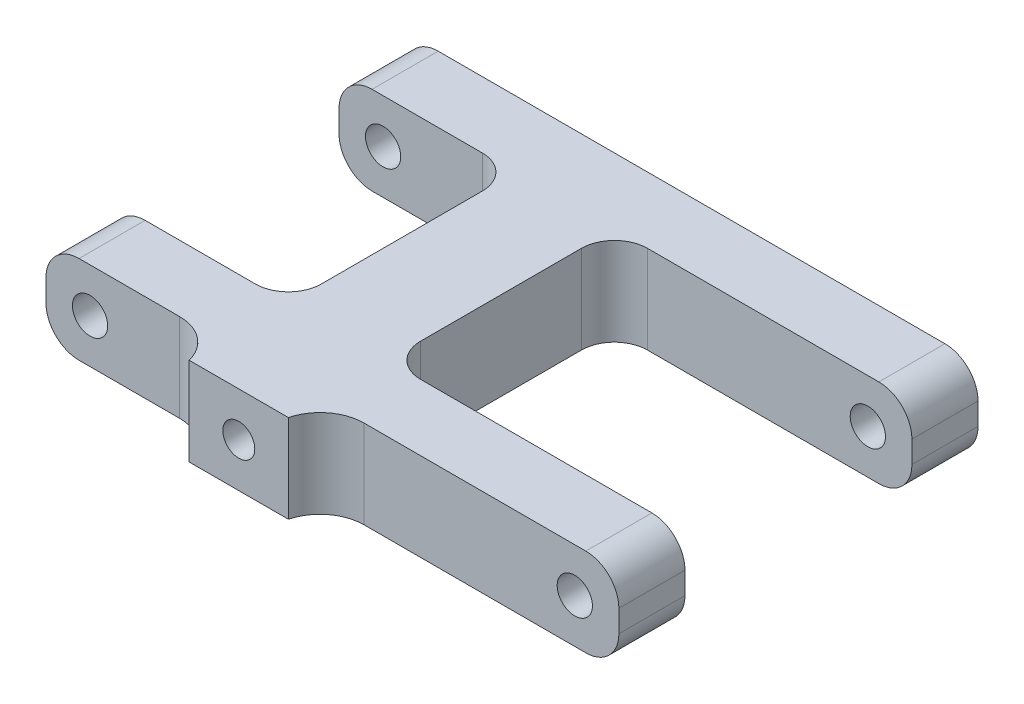
SolidWorks part; units mm, degrees
ref_plane "Front" through (0, 0, 0) normal (0, 0, 1) x (1, 0, 0)
ref_plane "Top" through (0, 0, 0) normal (0, 1, 0) x (1, 0, 0)
ref_plane "Right" through (0, 0, 0) normal (1, 0, 0) x (0, 0, -1)
sketch "Sketch1" plane through (0, 0, 0) normal (0, 1, 0) x (1, 0, 0)
  line L1 (0, 0) -> (52, 0)
  line L2 (0, 0) -> (0, -32.6)
  line L3 (0, -32.6) -> (52, -32.6)
  line L4 (52, 0) -> (52, -32.6)
  dimension "D1" = 32.6
  dimension "D2" = 52
extrude "Boss-Extrude1" add sketch "Sketch1" along normal blind 8
sketch "Sketch2" plane through (52, 0, 0) normal (1, 0, 0) x (0, 0, -1)
  line L0 (-32.6, 8) -> (0, 8) construction
  line L1 (-26.6, 8) -> (-6, 8)
  line L2 (-26.6, 8) -> (-26.6, 0)
  line L3 (-26.6, 0) -> (-6, 0)
  line L4 (-6, 8) -> (-6, 0)
  line L5 (-32.6, 0) -> (0, 0) construction
  line L6 (-32.6, 8) -> (-32.6, 0) construction
  line L7 (0, 8) -> (0, 0) construction
  dimension "D1" = 6
  dimension "D2" = 6
extrude "Cut-Extrude1" cut sketch "Sketch2" against normal blind 27
sketch "Sketch3" plane through (0, 0, 0) normal (-1, 0, 0) x (0, 0, 1)
  line L0 (0, 8) -> (32.6, 8) construction
  line L1 (6, 8) -> (26.6, 8)
  line L2 (6, 8) -> (6, 0)
  line L3 (6, 0) -> (26.6, 0)
  line L4 (26.6, 8) -> (26.6, 0)
  line L5 (0, 0) -> (32.6, 0) construction
  line L6 (32.6, 8) -> (32.6, 0) construction
  line L7 (0, 8) -> (0, 0) construction
  dimension "D1" = 6
  dimension "D2" = 6
extrude "Cut-Extrude2" cut sketch "Sketch3" against normal blind 16
sketch "Sketch5" plane through (0, 0, 32.6) normal (0, 0, 1) x (1, 0, 0)
  line L0 (0, 8) -> (52, 8) construction
  line L1 (0, 8) -> (0, 0) construction
  circle A0 centre (4, 4) radius 1.6
  circle A1 centre (48, 4) radius 1.6
  dimension "D1" = 3.2
  dimension "D2" = 4
  dimension "D3" = 4
  dimension "D4" = 2
extrude "Cut-Extrude4" cut sketch "Sketch5" against normal through all
fillet "Fillet1" radius 3 8 edges at (0, 0, 29.6) (0, 8, 29.6) (0, 0, 3) (0, 8, 3) (52, 8, 3) (52, 0, 3) (52, 0, 29.6) (52, 8, 29.6)
fillet "Fillet2" radius 3 4 edges at (25, 4, 26.6) (25, 4, 6) (16, 4, 26.6) (16, 4, 6)
sketch "Sketch8" plane through (0, 0, 32.6) normal (0, 0, 1) x (1, 0, 0)
  line L0 (3, 8) -> (49, 8) construction
  line L1 (16, 8) -> (25, 8)
  line L2 (16, 8) -> (16, 0)
  line L3 (16, 0) -> (25, 0)
  line L4 (25, 8) -> (25, 0)
  line L5 (3, 0) -> (49, 0) construction
  line L6 (52, 5) -> (52, 3) construction
  line L7 (0, 5) -> (0, 3) construction
  dimension "D1" = 27
  dimension "D2" = 16
extrude "Boss-Extrude2" add sketch "Sketch8" along normal blind 3
sketch "Sketch6" plane through (0, 0, 32.6) normal (0, 0, 1) x (1, 0, 0)
  line L0 (3, 8) -> (16, 8) construction
  line L2 (52, 5) -> (52, 3) construction
  circle A0 centre (20.5, 4) radius 1.45
  dimension "D1" = 2.9
  dimension "D2" = 4
  dimension "D3" = 31.5
extrude "Cut-Extrude5" cut sketch "Sketch6" against normal blind 15 and the other way blind 4
fillet "Fillet3" radius 4 2 edges at (25, 4, 32.6) (16, 4, 32.6)
